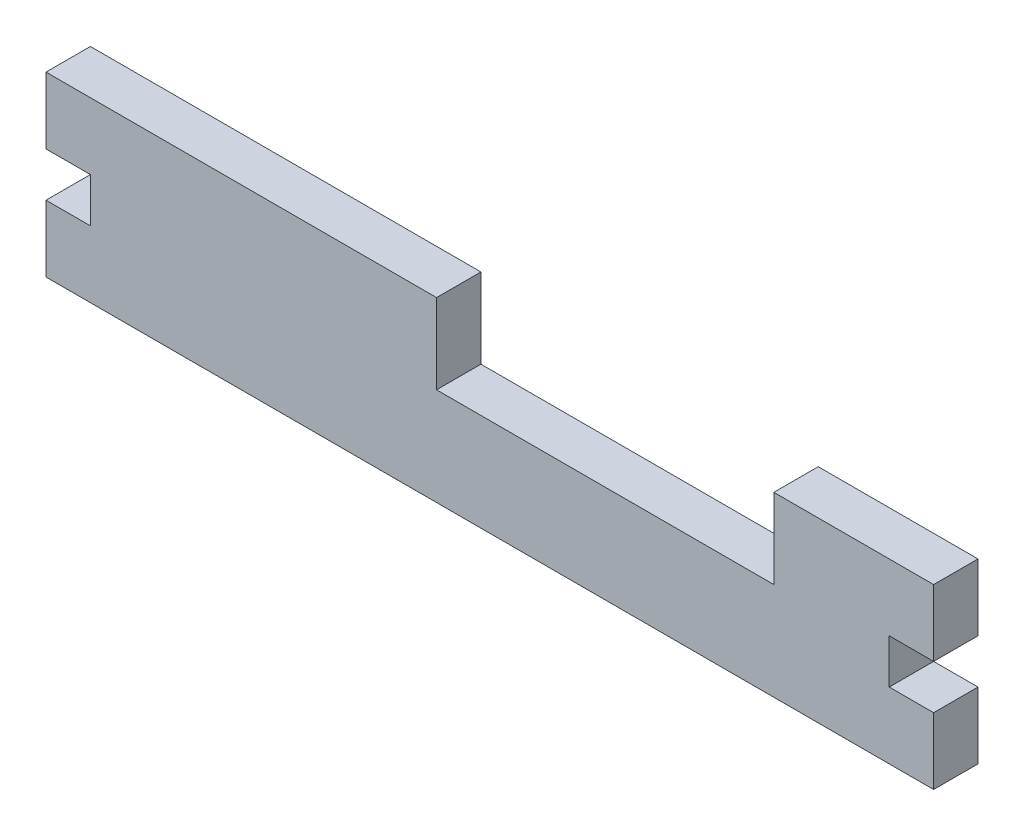
SolidWorks part; units mm, degrees
ref_plane "Plan de face" through (0, 0, 0) normal (0, 0, 1) x (1, 0, 0)
ref_plane "Plan de dessus" through (0, 0, 0) normal (0, 1, 0) x (1, 0, 0)
ref_plane "Plan de droite" through (0, 0, 0) normal (1, 0, 0) x (0, 0, -1)
sketch "Esquisse1" plane through (0, 0, 0) normal (0, 0, 1) x (1, 0, 0)
  line L0 (45, 0) -> (45, 20) construction
  line L1 (0, 0) -> (90, 0)
  line L2 (0, 7.5) -> (0, 12.5)
  line L3 (0, 20) -> (39, 20)
  line L4 (90, 7.5) -> (90, 12.5)
  line L5 (90, 0) -> (95, 0)
  line L6 (0, 20) -> (-5, 20)
  line L7 (77, 20) -> (90, 20)
  line L8 (0, 12.5) -> (-5, 12.5)
  line L9 (-5, 20) -> (-5, 12.5)
  line L10 (0, 0) -> (-5, 0)
  line L12 (0, 7.5) -> (-5, 7.5)
  line L13 (-5, 0) -> (-5, 7.5)
  line L14 (95, 0) -> (95, 7.5)
  line L15 (90, 7.5) -> (95, 7.5)
  line L16 (90, 12.5) -> (95, 12.5)
  line L17 (95, 20) -> (95, 12.5)
  line L18 (90, 20) -> (95, 20)
  line L19 (77, 20) -> (77, 11)
  line L20 (77, 11) -> (39, 11)
  line L21 (39, 20) -> (39, 11)
  dimension "D1" = 90
  dimension "D2" = 20
  dimension "D3" = 13
  dimension "D4" = 7.5
  dimension "D5" = 5
  dimension "D6" = 38
  dimension "D7" = 9
extrude "Boss.-Extru.1" add sketch "Esquisse1" along normal blind 5
